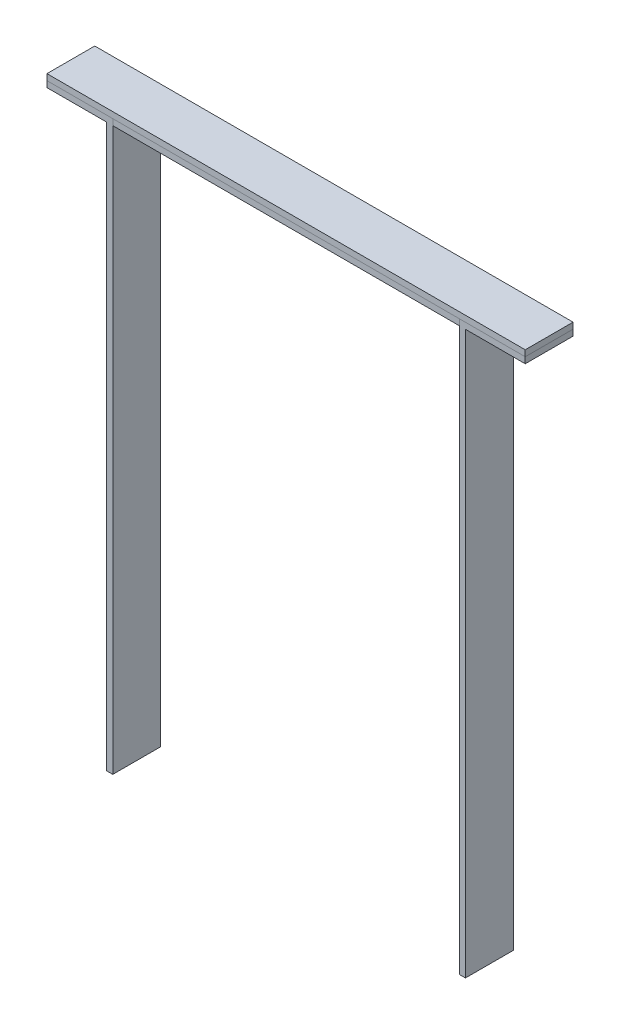
SolidWorks part; units mm, degrees
ref_plane "Front Plane" through (0, 0, 0) normal (0, 0, 1) x (1, 0, 0)
ref_plane "Top Plane" through (0, 0, 0) normal (0, 1, 0) x (1, 0, 0)
ref_plane "Right Plane" through (0, 0, 0) normal (1, 0, 0) x (0, 0, -1)
sketch "Sketch2" plane through (0, 0, 0) normal (0, 0, 1) x (1, 0, 0)
  line L0 (0, 0) -> (0, 117.46)
  line L1 (0, 117.46) -> (-12.5, 117.46)
  line L2 (-12.5, 117.46) -> (-12.5, 118.73)
  line L3 (-12.5, 118.73) -> (1.27, 118.73)
  line L4 (1.27, 118.73) -> (1.27, 0)
  line L5 (1.27, 0) -> (0, 0)
  line L6 (-12.5, 118.73) -> (-12.5, 120)
  line L7 (-12.5, 120) -> (87.5, 120)
  line L8 (87.5, 120) -> (87.5, 118.73)
  line L9 (87.5, 118.73) -> (-12.5, 118.73)
  line L10 (87.5, 118.73) -> (87.5, 117.46)
  line L11 (87.5, 117.46) -> (75, 117.46)
  line L12 (75, 117.46) -> (75, 0)
  line L13 (75, 0) -> (73.73, 0)
  line L14 (73.73, 0) -> (73.73, 118.73)
  line L15 (73.73, 118.73) -> (87.5, 118.73)
  line L17 (1.27, 118.73) -> (73.73, 118.73)
  line L18 (1.27, 118.73) -> (1.27, 117.46)
  line L19 (1.27, 117.46) -> (73.73, 117.46)
  line L20 (73.73, 118.73) -> (73.73, 117.46)
  point P17 (44.4115, 0)
  point P18 (0, 0)
  dimension "D1" = 1.27
  dimension "D2" = 1.27
  dimension "D3" = 100
  dimension "D4" = 12.5
  dimension "D5" = 120
extrude "Boss-Extrude1" add sketch "Sketch2" along normal blind 10 contours L5 L4 L3 L2 L1 L0 | L14 L13 L12 L11 L10 L9 region at (1.1953, 58.73, 0) region at (74.9253, 118.095, 0)
extrude "Boss-Extrude2" add sketch "Sketch2<4>" along normal blind 10 separate body contours L4 L19 L14 L9 region at (37.5, 118.095, 0)
sketch "Sketch2<4>" plane through (0, 0, 0) normal (0, 0, 1) x (1, 0, 0) same geometry as "Sketch2"
extrude "Boss-Extrude3" add sketch "Sketch2<5>" along normal blind 10 separate body contours L9 L8 L7 L6 L3 region at (37.5, 119.365, 0)
sketch "Sketch2<5>" plane through (0, 0, 0) normal (0, 0, 1) x (1, 0, 0) same geometry as "Sketch2"
